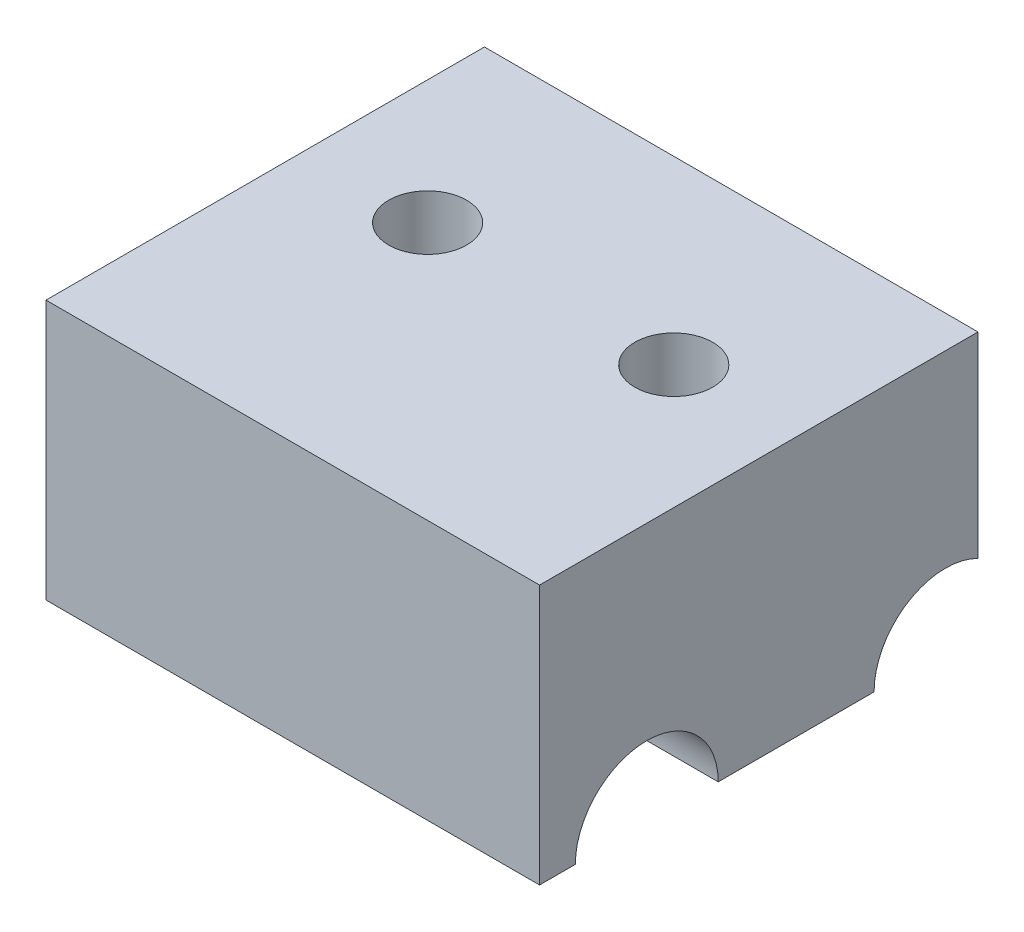
SolidWorks part; units mm, degrees
ref_plane "Front Plane" through (0, 0, 0) normal (0, 0, 1) x (1, 0, 0)
ref_plane "Top Plane" through (0, 0, 0) normal (0, 1, 0) x (1, 0, 0)
ref_plane "Right Plane" through (0, 0, 0) normal (1, 0, 0) x (0, 0, -1)
sketch "Sketch6" plane through (0, 0, 0) normal (0, 1, 0) x (1, 0, 0)
  line L0 (0, 0) -> (0, 5)
  line L1 (0, 5) -> (19, 5)
  line L2 (19, 5) -> (19, 2.75)
  line L6 (19, 2.75) -> (16, 2.75)
  line L7 (16, 2.75) -> (15, 2.25)
  line L8 (15, 2.25) -> (15, 2.75)
  line L9 (15, 2.75) -> (9, 2.75)
  line L10 (9, 2.75) -> (8, 2.25)
  line L11 (8, 2.25) -> (8, 2.75)
  line L12 (8, 2.75) -> (0, 2.75)
  line L18 (0, 0) -> (15, 0)
  dimension "D1" = 0.5
  dimension "D2" = 19
  dimension "D3" = 3
  dimension "D4" = 5
  dimension "D5" = 2.25
  dimension "D6" = 2.25
  dimension "D7" = 2.25
  dimension "D10" = 1
  dimension "D11" = 1
  dimension "D12" = 6
  dimension "D13" = 8
  dimension "D20" = 15
revolve "Revolve1" add sketch "Sketch6" angle 180 about L18 region at (9.527, 0, -3.8601)
sketch "Sketch9" plane through (0, 0, 0) normal (0, 0, 1) x (1, 0, 0)
  line L0 (0, 0) -> (0, 3.25)
  line L1 (0, 3.25) -> (0, 5)
  line L2 (0, 5) -> (19, 5)
  line L3 (19, 5) -> (19, 2.75)
  line L4 (19, 2.75) -> (19, 0)
  line L5 (19, 0) -> (0, 0)
  line L6 (0, 3.25) -> (19, 2.75)
  dimension "D1" = 3.25
extrude "Boss-Extrude1" add sketch "Sketch9" along normal blind 9.25 and the other way blind 9.25 contours L1 L6 L3 L2 region at (9.8958, 3.9948, 0)
extrude "Boss-Extrude2" add sketch "Sketch9<3>" along normal blind 5.75 from offset 3.5 contours L6 L0 L5 L4 region at (9.2361, 1.5035, 0)
sketch "Sketch9<3>" plane through (0, 0, 0) normal (0, 0, 1) x (1, 0, 0) same geometry as "Sketch9"
extrude "Boss-Extrude3" add sketch "Sketch9<4>" against normal blind 5.75 from offset 3.5 contours L6 L0 L5 L4 region at (9.2361, 1.5035, 0) offset against normal yes
sketch "Sketch9<4>" plane through (0, 0, 0) normal (0, 0, 1) x (1, 0, 0) same geometry as "Sketch9"
sketch "Sketch14" plane through (0, 0, 0) normal (-1, 0, 0) x (0, 0, 1)
  line L0 (-9.25, 5) -> (9.25, 5) construction
  line L1 (-9.25, 0) -> (-6.75, 0)
  line L2 (-9.25, 0) -> (-9.25, 5)
  line L3 (-9.25, 5) -> (-6.75, 5)
  line L4 (-6.75, 0) -> (-6.75, 5)
  dimension "D1" = 2.5
extrude "Cut-Extrude10" cut sketch "Sketch14" against normal through all
ref_plane "Plane3" through (0, 0, -5.75) normal (0, 0, 1) x (1, 0, 0)
mirror "Mirror4" about plane through (0, 0, -5.75) normal (0, 0, 1) of bodies 150 146
sketch "Sketch13" plane through (0, 0, 0) normal (-1, 0, 0) x (0, 0, 1)
  line L0 (-2.75, 0) -> (-8.75, 0) construction
  line L1 (-2.75, 0) -> (2.75, 0)
  line L2 (-2.75, 0) -> (-2.75, 2.75)
  line L3 (-2.75, 2.75) -> (2.75, 2.75)
  line L4 (2.75, 0) -> (2.75, 2.75)
  point P6 (0, 0)
  dimension "D1" = 5.5
  dimension "D2" = 2.75
extrude "Cut-Extrude9" cut sketch "Sketch13" against normal blind 1.75
sketch "Sketch15" plane through (0, 5, 0) normal (0, 1, 0) x (1, 0, 0)
  line L0 (0, 20.75) -> (0, -9.25) construction
  line L1 (19, 20.75) -> (0, 20.75)
  line L2 (19, 20.75) -> (19, 12.75)
  line L3 (19, 12.75) -> (0, 12.75)
  line L4 (0, 20.75) -> (0, 12.75)
  dimension "D1" = 8
extrude "Cut-Extrude11" cut sketch "Sketch15" against normal through all
sketch "Sketch16" plane through (0, 0, 0) normal (-1, 0, 0) x (0, 0, 1)
  line L0 (-12.75, 5) -> (9.25, 5) construction
  line L1 (9.25, 0) -> (4.1274, 0)
  line L2 (9.25, 0) -> (9.25, 5)
  line L3 (9.25, 5) -> (4.1274, 5)
  line L4 (4.1274, 0) -> (4.1274, 5)
extrude "Cut-Extrude12" cut sketch "Sketch16" against normal through all
sketch "Sketch17" plane through (0, 5, 0) normal (0, 1, 0) x (1, 0, 0)
  line L1 (0, -4.1274) -> (19, -4.1274)
  line L2 (0, -4.1274) -> (0, 12.75)
  line L3 (0, 12.75) -> (19, 12.75)
  line L4 (19, -4.1274) -> (19, 12.75)
extrude "Boss-Extrude4" add sketch "Sketch17" along normal blind 5
sketch "Sketch18" plane through (0, 10, 0) normal (0, 1, 0) x (1, 0, 0)
  line L0 (19, -4.1274) -> (19, 12.75) construction
  line L1 (0, 12.75) -> (0, -4.1274) construction
  line L2 (0, -4.1274) -> (19, -4.1274) construction
  circle A0 centre (4.7625, 5.8008) radius 1.5
  circle A1 centre (14.2375, 5.8008) radius 1.5
  point P4 (0, 0)
  point P11 (0, 0)
  dimension "D1" = 3
  dimension "D2" = 3
  dimension "D3" = 4.7625
  dimension "D4" = 4.7625
  dimension "D5" = 9.9282
extrude "Cut-Extrude13" cut sketch "Sketch18" against normal through all
